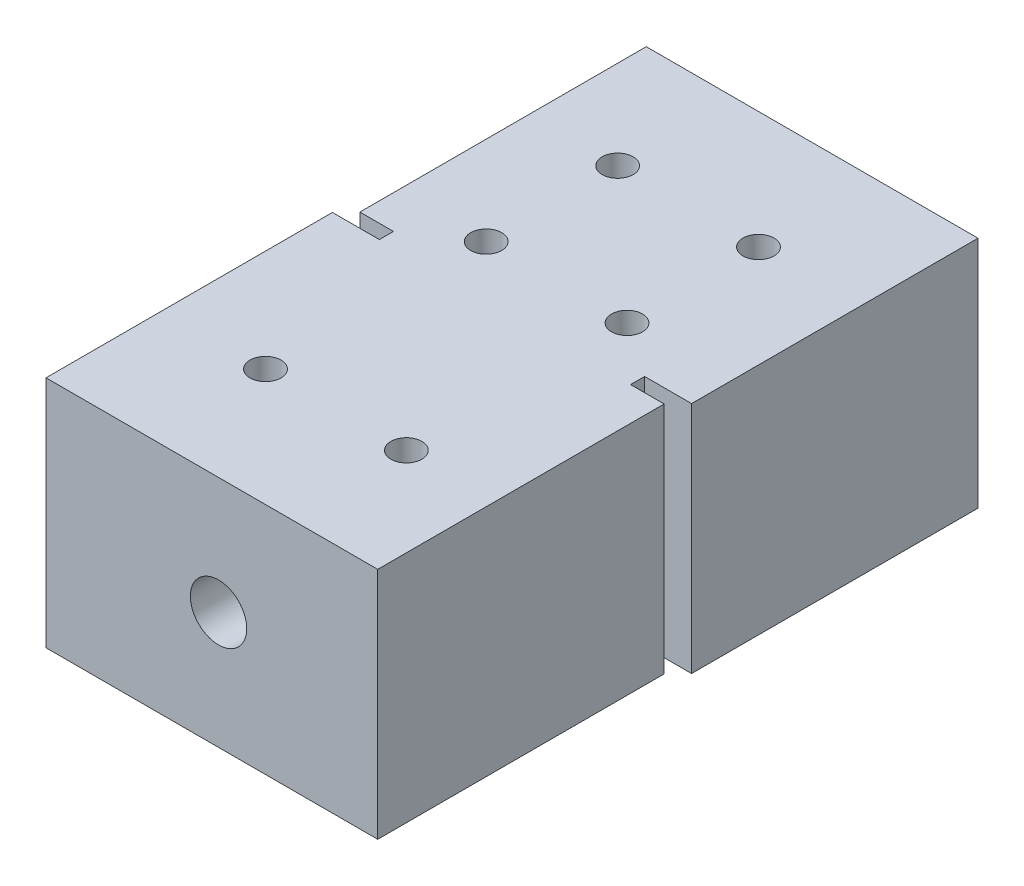
SolidWorks part; units mm, degrees
material "Beech"
ref_plane "Front Plane" through (0, 0, 0) normal (0, 0, 1) x (1, 0, 0)
ref_plane "Top Plane" through (0, 0, 0) normal (0, 1, 0) x (1, 0, 0)
ref_plane "Right Plane" through (0, 0, 0) normal (1, 0, 0) x (0, 0, -1)
sketch "Sketch1" plane through (0, 0, 0) normal (0, 0, 1) x (1, 0, 0)
  line L1 (0, 0) -> (73.5, 0)
  line L2 (0, 0) -> (0, 49.8)
  line L3 (0, 49.8) -> (73.5, 49.8)
  line L4 (73.5, 0) -> (73.5, 49.8)
  dimension "D1" = 73.5
  dimension "D2" = 49.8
extrude "slider body" add sketch "Sketch1" along normal blind 125
sketch "Sketch2" plane through (0, 0, 0) normal (0, 0, -1) x (-1, 0, 0)
  line L0 (-73.5, 49.8) -> (0, 0) construction
  line L1 (-73.5, 0) -> (0, 49.8) construction
  circle A0 centre (-36.75, 24.9) radius 11
  dimension "D1" = 22
extrude "lead nut inset" cut sketch "Sketch2" against normal blind 15
sketch "Sketch3" plane through (0, 0, 15) normal (0, 0, -1) x (-1, 0, 0)
  circle A0 centre (-36.75, 24.9) radius 6
  circle A1 centre (-36.75, 24.9) radius 11 construction
  dimension "D1" = 12
extrude "leadscrew clearance" cut sketch "Sketch3" against normal through all
sketch "Sketch9" plane through (0, 0, 0) normal (0, -1, 0) x (1, 0, 0)
  line L0 (73.5, 125) -> (73.5, 0) construction
  line L1 (73.5, 64) -> (63.5, 64)
  line L2 (73.5, 64) -> (73.5, 61)
  line L3 (73.5, 61) -> (63.5, 61)
  line L4 (63.5, 64) -> (63.5, 61)
  point P6 (73.5, 62.5)
  point P7 (73.5, 62.5)
  dimension "D1" = 10
  dimension "D2" = 3
extrude "decoupling slit" cut sketch "Sketch9" against normal through all
hole_wizard "bolt clearance holes" positions "Sketch4" profile "Sketch6" hole size "M6" standard "ANSI Metric" end condition through all
sketch "Sketch4" plane through (0, 49.8, 0) normal (0, 1, 0) x (1, 0, 0)
  line L1 (51.75, -100) -> (21.75, -100)
  line L2 (51.75, -100) -> (51.75, -25)
  line L3 (51.75, -25) -> (21.75, -25)
  line L4 (21.75, -100) -> (21.75, -25)
  line L10 (21.75, -62.5) -> (0, -62.5)
  line L11 (0, -125) -> (0, 0) construction
  line L13 (36.75, -100) -> (36.75, -125)
  line L14 (73.5, -125) -> (0, -125) construction
  point P1 (51.75, -100)
  point P2 (21.75, -25)
  point P47 (51.75, -25)
  point P48 (21.75, -100)
  point P72 (21.75, -53)
  point P74 (51.75, -53)
  dimension "D1" = 30
  dimension "D2" = 75
  dimension "D3" = 28
sketch "Sketch6" plane through (51.75, 49.8, 100) normal (1, 0, 0) x (0, 0, 1)
  line L0 (0, 0) -> (0, 49.8)
  line L1 (0, 49.8) -> (3.3, 49.8)
  line L2 (3.3, 49.8) -> (3.3, 0)
  line L5 (3.3, 0) -> (0, 0)
  line L11 (0, -6.35) -> (0, 107.95) construction
  dimension "Thru Hole Dia." = 6.6
  dimension "Thru Hole Depth" = 49.8
sketch "Sketch7" plane through (0, 0, 0) normal (0, -1, 0) x (1, 0, 0)
  circle A0 centre (21.75, 100) radius 6
  circle A1 centre (51.75, 100) radius 6
  circle A2 centre (51.75, 25) radius 6
  circle A3 centre (21.75, 25) radius 6
  dimension "D1" = 12
extrude "nut clearance counterbores" [suppressed] cut sketch "Sketch7" against normal blind 10
ref_plane "midplane along length" through (36.75, 0, 0) normal (-1, 0, 0) x (0, 0, 1)
mirror "mirror slit" about plane through (36.75, 0, 0) normal (-1, 0, 0) of "decoupling slit"
sketch "Sketch10" plane through (0, 0, 0) normal (0, -1, 0) x (1, 0, 0)
  line L0 (73.5, 64) -> (63.5, 64) construction
  line L1 (73.5, 125) -> (70.65, 125)
  line L2 (73.5, 125) -> (73.5, 64)
  line L3 (73.5, 64) -> (70.65, 64)
  line L4 (70.65, 125) -> (70.65, 64)
  line L5 (0, 0) -> (73.5, 0) construction
  line L6 (0, 61) -> (2.85, 61)
  line L7 (0, 61) -> (0, 0)
  line L8 (0, 0) -> (2.85, 0)
  line L9 (2.85, 61) -> (2.85, 0)
  dimension "D1" = 2.85
extrude "neoprene inlay" cut sketch "Sketch10" against normal through all
equation "\"board_thickness\" = 18mm"
equation "\"way_width\"= 75mm"
equation "\"way_thickness\"= 50mm"
equation "\"radial_clearance\"= 0.1mm"
equation "\"slider_width\"= \"way_width\"-2* \"radial_clearance\" - 2*0.65"
equation "\"slider_thickness\" = \"way_thickness\" - 2 * \"radial_clearance\""
equation "\"column_width\"= \"way_width\" + 2 * \"board_thickness\""
equation "\"boxway_slot_width\" = 50mm"
equation "\"keeper_rail_width\" = (\"column_width\" - \"boxway_slot_width\")/2"
equation "\"slider_length\" = 125mm"
equation "\"D1@Sketch1\"=\"slider_width\""
equation "\"D2@Sketch1\"=\"slider_thickness\""
equation "\"D1@slider body\" = \"slider_length\""
equation "\"nut_diameter\"= 22mm"
equation "\"nut_length\"= 15mm"
equation "\"D1@Sketch2\"=\"nut_diameter\""
equation "\"D1@lead nut inset\" = \"nut_length\""
equation "\"leadscrew_diameter\"= 10mm"
equation "\"leadscrew_radial_clearance\"= 1mm"
equation "\"D1@Sketch3\"=\"leadscrew_diameter\"+2* \"leadscrew_radial_clearance\""
equation "\"bearing_bolt_pattern_width\" = 30mm"
equation "\"bearing_bolt_pattern_height\" = 75mm"
equation "\"desktop_bolt_pattern_width\" = 30mm"
equation "\"desktop_bolt_pattern_height\" = 30mm"
equation "\"D1@Sketch4\"=\"bearing_bolt_pattern_width\""
equation "\"D2@Sketch4\"=\"bearing_bolt_pattern_height\""
equation "\"bearing_bolt_nut_counterbore_diameter\" = 12mm"
equation "\"bearing_bolt_nut_counterbore_depth\"= 10mm"
equation "\"D1@Sketch7\"=\"bearing_bolt_nut_counterbore_diameter\""
equation "\"D1@nut clearance counterbores\" = \"bearing_bolt_nut_counterbore_depth\""
equation "\"D1@Sketch10\"=3.5-0.65"
